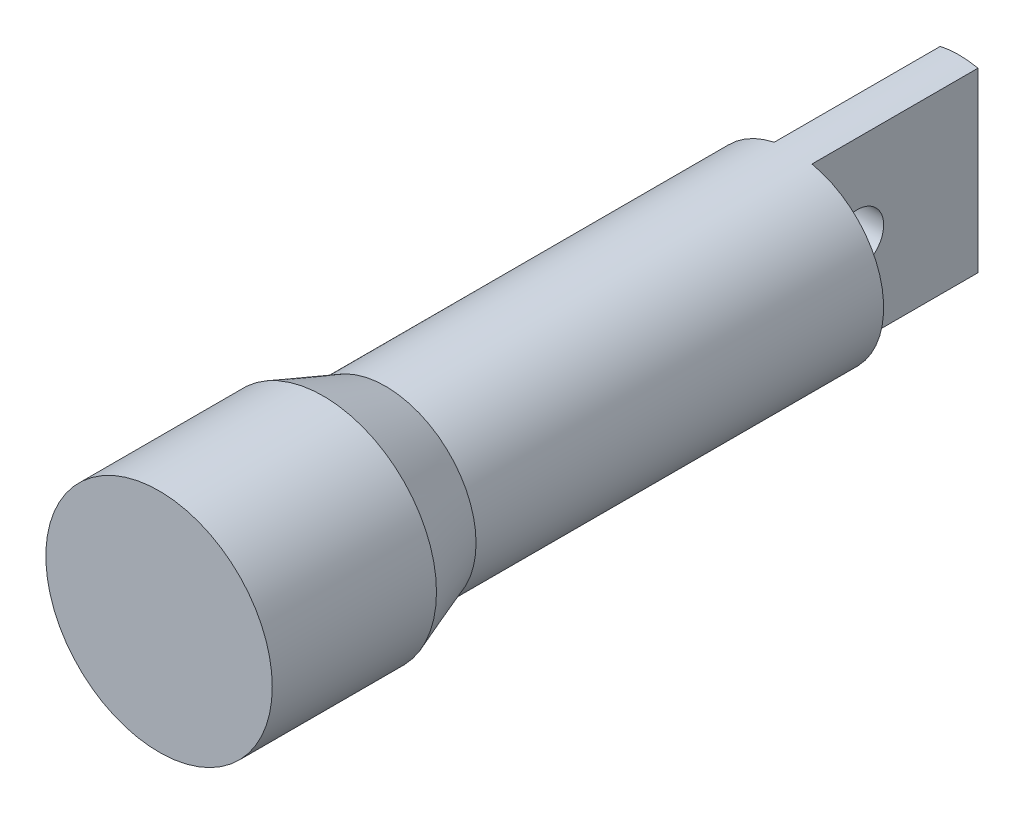
SolidWorks part; units mm, degrees
ref_plane "Front Plane" through (0, 0, 0) normal (0, 0, 1) x (1, 0, 0)
ref_plane "Top Plane" through (0, 0, 0) normal (0, 1, 0) x (1, 0, 0)
ref_plane "Right Plane" through (0, 0, 0) normal (1, 0, 0) x (0, 0, -1)
sketch "Sketch1" plane through (0, 0, 0) normal (0, 0, 1) x (1, 0, 0)
  circle A0 centre (0, 0) radius 6
  dimension "D1" = 12
extrude "Boss-Extrude1" add sketch "Sketch1" along normal blind 27
sketch "Sketch2" plane through (0, 0, 0) normal (0, 0, -1) x (-1, 0, 0)
  line L1 (-1.25, -5.8683) -> (1.25, -5.8683) construction
  line L2 (-1.25, -5.8683) -> (-1.25, 5.8683)
  line L3 (-1.25, 5.8683) -> (1.25, 5.8683) construction
  line L4 (1.25, -5.8683) -> (1.25, 5.8683)
  line L5 (-1.25, -5.8683) -> (1.25, 5.8683) construction
  line L6 (-1.25, 5.8683) -> (1.25, -5.8683) construction
  arc A0 (1.25, 5.8683) -> (-1.25, 5.8683) centre (0, 0) ccw
  circle A1 centre (0, 0) radius 6
  arc A2 (-1.25, -5.8683) -> (1.25, -5.8683) centre (0, 0) ccw
  dimension "D2" = 2.5
  dimension "D1" = 0
extrude "Boss-Extrude2" add sketch "Sketch2" along normal blind 11
sketch "Sketch3" plane through (1.25, 0, 0) normal (1, 0, 0) x (0, 0, -1)
  line L0 (3, 0) -> (0, 0) construction
  circle A0 centre (3, 0) radius 1.75
  dimension "D2" = 3.5
  dimension "D1" = 3
extrude "Cut-Extrude1" cut sketch "Sketch3" against normal blind 6
sketch "Sketch4" plane through (0, 0, 27) normal (0, 0, 1) x (1, 0, 0)
  circle A0 centre (0, 0) radius 7.5
  dimension "D1" = 15
extrude "Boss-Extrude3" add sketch "Sketch4" along normal blind 15
chamfer "Chamfer1" distance 1.5 angle 70 1 edges at (7.5, 0, 27) first distance on face at (6, 0, 27)
